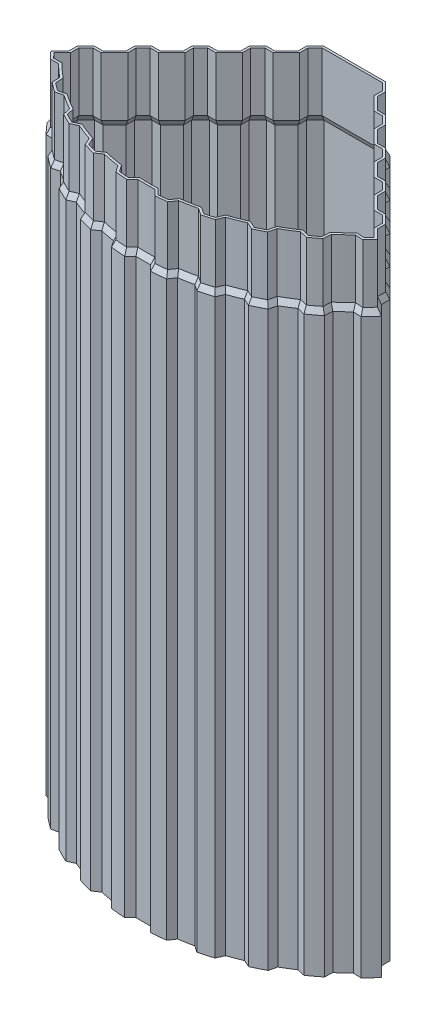
SolidWorks part; units mm, degrees
ref_plane "Front Plane" through (0, 0, 0) normal (0, 0, 1) x (1, 0, 0)
ref_plane "Top Plane" through (0, 0, 0) normal (0, 1, 0) x (1, 0, 0)
ref_plane "Right Plane" through (0, 0, 0) normal (1, 0, 0) x (0, 0, -1)
sketch "Sketch1" plane through (0, 0, 0) normal (0, 1, 0) x (1, 0, 0)
  line L3 (0, 0) -> (0, -48.7896) construction
  line L4 (0, -48.7896) -> (-56.9612, -48.7896) construction
  line L5 (0, -48.7896) -> (56.9612, -48.7896) construction
  line L11 (-11, 0) -> (11, 0)
  line L12 (-14.4647, -3.4647) -> (-11, 0)
  line L14 (-14.4647, -3.4647) -> (-14.4647, -6.2932)
  line L15 (-14.4647, -6.2932) -> (-17.9295, -9.7579)
  line L16 (-17.9295, -9.7579) -> (-20.7579, -9.7579)
  line L17 (-20.7579, -9.7579) -> (-24.2227, -13.2227)
  line L18 (-30.5158, -19.5158) -> (-33.9806, -22.9806)
  line L19 (-27.6874, -19.5158) -> (-30.5158, -19.5158)
  line L20 (-24.2227, -16.0511) -> (-27.6874, -19.5158)
  line L21 (-24.2227, -13.2227) -> (-24.2227, -16.0511)
  line L22 (-40.2738, -29.2738) -> (-43.7385, -32.7385)
  line L23 (-37.4453, -29.2738) -> (-40.2738, -29.2738)
  line L24 (-33.9806, -25.809) -> (-37.4453, -29.2738)
  line L25 (-33.9806, -22.9806) -> (-33.9806, -25.809)
  line L26 (-50.0317, -39.0317) -> (-53.4964, -42.4964)
  line L27 (-47.2033, -39.0317) -> (-50.0317, -39.0317)
  line L28 (-43.7385, -35.5669) -> (-47.2033, -39.0317)
  line L29 (-43.7385, -32.7385) -> (-43.7385, -35.5669)
  line L31 (53.4964, -42.4964) -> (53.4964, -45.3249)
  line L32 (-53.4964, -45.3249) -> (-56.9612, -48.7896)
  line L33 (-53.4964, -42.4964) -> (-53.4964, -45.3249)
  line L34 (-56.9612, -48.7896) -> (-59.7896, -48.7896) [skipped]
  line L35 (-59.7896, -48.7896) -> (-63.2543, -52.2543) [skipped]
  line L36 (53.4964, -45.3249) -> (56.9612, -48.7896)
  line L38 (43.7385, -32.7385) -> (43.7385, -35.5669)
  line L39 (43.7385, -35.5669) -> (47.2033, -39.0317)
  line L40 (47.2033, -39.0317) -> (50.0317, -39.0317)
  line L41 (50.0317, -39.0317) -> (53.4964, -42.4964)
  line L42 (33.9806, -22.9806) -> (33.9806, -25.809)
  line L43 (33.9806, -25.809) -> (37.4453, -29.2738)
  line L44 (37.4453, -29.2738) -> (40.2738, -29.2738)
  line L45 (40.2738, -29.2738) -> (43.7385, -32.7385)
  line L46 (24.2227, -13.2227) -> (24.2227, -16.0511)
  line L47 (24.2227, -16.0511) -> (27.6874, -19.5158)
  line L48 (27.6874, -19.5158) -> (30.5158, -19.5158)
  line L49 (30.5158, -19.5158) -> (33.9806, -22.9806)
  line L50 (20.7579, -9.7579) -> (24.2227, -13.2227)
  line L51 (17.9295, -9.7579) -> (20.7579, -9.7579)
  line L52 (14.4647, -6.2932) -> (17.9295, -9.7579)
  line L53 (14.4647, -3.4647) -> (14.4647, -6.2932)
  line L54 (11, 0) -> (14.4647, -3.4647)
  line L55 (-53.6221, -52.4373) -> (-50.9199, -52.3083)
  line L56 (-47.2198, -55.6713) -> (-47.0908, -58.3734)
  line L57 (-53.6221, -52.4373) -> (-56.9612, -48.7896) construction
  line L58 (-43.0968, -61.3813) -> (-40.4641, -60.759)
  line L59 (-36.2101, -63.3864) -> (-35.5877, -66.019)
  line L60 (-31.1098, -68.2435) -> (-28.6359, -67.149)
  line L61 (-23.9722, -68.9517) -> (-22.8776, -71.4256)
  line L62 (-18.0677, -72.7912) -> (-15.8365, -71.2615)
  line L63 (-10.9213, -72.1784) -> (-9.3916, -74.4097)
  line L64 (-4.4129, -74.8701) -> (-2.5, -72.9572)
  line L65 (2.5, -72.9572) -> (4.4129, -74.8701)
  line L66 (9.3916, -74.4097) -> (10.9213, -72.1784)
  line L67 (15.8365, -71.2615) -> (18.0677, -72.7912)
  line L68 (22.8776, -71.4256) -> (23.9722, -68.9517)
  line L69 (28.6359, -67.149) -> (31.1098, -68.2435)
  line L70 (35.5877, -66.019) -> (36.2101, -63.3864)
  line L71 (40.4641, -60.759) -> (43.0968, -61.3813)
  line L72 (47.0908, -58.3734) -> (47.2198, -55.6713)
  line L73 (50.9199, -52.3083) -> (53.6221, -52.4373)
  line L74 (53.6221, -52.4373) -> (56.9612, -48.7896) construction
  arc A0 (-56.9612, -48.7896) -> (-53.6221, -52.4373) centre (0, 0) ccw
  arc A2 (-36.2902, -47.7807) -> (36.2902, -47.7807) centre (0, 0) ccw construction
  circle A3 centre (0, -59.9997) radius 1.7
  circle A4 centre (-34.922, -48.7896) radius 1.7
  circle A5 centre (34.922, -48.7896) radius 1.7
  circle A6 centre (0, -26) radius 1.7
  arc A8 (-55.5426, -47.3711) -> (-54.3008, -48.7896) centre (0, 0) ccw construction
  arc A9 (-47.0908, -58.3734) -> (-43.0968, -61.3813) centre (0, 0) ccw
  arc A10 (-50.9199, -52.3083) -> (-47.2198, -55.6713) centre (0, 0) ccw
  arc A11 (-40.4641, -60.759) -> (-36.2101, -63.3864) centre (0, 0) ccw
  arc A12 (-35.5877, -66.019) -> (-31.1098, -68.2435) centre (0, 0) ccw
  arc A13 (-28.6359, -67.149) -> (-23.9722, -68.9517) centre (0, 0) ccw
  arc A14 (-22.8776, -71.4256) -> (-18.0677, -72.7912) centre (0, 0) ccw
  arc A15 (-15.8365, -71.2615) -> (-10.9213, -72.1784) centre (0, 0) ccw
  arc A16 (-9.3916, -74.4097) -> (-4.4129, -74.8701) centre (0, 0) ccw
  arc A17 (-2.5, -72.9572) -> (2.5, -72.9572) centre (0, 0) ccw
  arc A18 (4.4129, -74.8701) -> (9.3916, -74.4097) centre (0, 0) ccw
  arc A19 (10.9213, -72.1784) -> (15.8365, -71.2615) centre (0, 0) ccw
  arc A20 (18.0677, -72.7912) -> (22.8776, -71.4256) centre (0, 0) ccw
  arc A21 (23.9722, -68.9517) -> (28.6359, -67.149) centre (0, 0) ccw
  arc A22 (31.1098, -68.2435) -> (35.5877, -66.019) centre (0, 0) ccw
  arc A23 (36.2101, -63.3864) -> (40.4641, -60.759) centre (0, 0) ccw
  arc A24 (43.0968, -61.3813) -> (47.0908, -58.3734) centre (0, 0) ccw
  arc A25 (47.2198, -55.6713) -> (50.9199, -52.3083) centre (0, 0) ccw
  arc A26 (53.6221, -52.4373) -> (56.9612, -48.7896) centre (0, 0) ccw
  arc A27 (54.3008, -48.7896) -> (55.5426, -47.3711) centre (0, 0) ccw construction
  point P36 (0, 0)
  point P42 (0, 0)
  point P97 (0, 0)
  point P98 (0, 0)
  point P101 (0, 0)
  dimension "D2" = 75
  dimension "D4" = 3.4
  dimension "D5" = 15.0003
  dimension "D7" = 135
  dimension "D9" = 2
  dimension "D1" = 22
  dimension "D3" = 135
  dimension "D6" = 26
  dimension "D8" = 2
  dimension "D10" = 90
  dimension "D12" = 90
  dimension "D13" = 5
  dimension "D14" = 4.8999
  dimension "D15" = 9
  dimension "D16" = 5
  dimension "D11" = 5
extrude "Extrude-Thin2" add sketch "Sketch1" along normal blind 195 thin contours L11 L54 L53 L52 L51 L50 L46 L47 L48 L49 L42 L43 L44 L45 L38 L39 L40 L41 L31 L36 A26 L73 A25 L72 A24 L71 A23 L70 A22 L69 A21 L68 A20 L67 A19 L66 A18 L65 A17 L64 A16 L63 A15 L62 A14 L61 A13 L60 A12 L59 A11 L58 A9 L56 A10 L55 A0 L32 L33 L26 L27 L28 L29 L22 L23 L24 L25 L18 L19 L20 L21 L17 L16 L15 L14 L12 thin type one direction reverse wall 0.8
ref_plane "Plane1" through (0, 197, 0) normal (0, 1, 0) x (1, 0, 0)
sketch "Sketch7" plane through (0, 197, 0) normal (0, 1, 0) x (1, 0, 0)
  line L6 (13.4647, -3.879) -> (10.5858, -1)
  line L7 (10.5858, -1) -> (-10.5858, -1)
  line L8 (13.4647, -3.879) -> (10.5858, -1)
  line L10 (10.5858, -1) -> (-10.5858, -1)
  line L47 (-10.5858, -1) -> (-13.4647, -3.879)
  line L48 (-10.5858, -1) -> (-13.4647, -3.879)
  line L49 (-13.4647, -3.879) -> (-13.4647, -6.7074)
  line L50 (-13.4647, -3.879) -> (-13.4647, -6.7074)
  line L51 (-13.4647, -6.7074) -> (-17.5153, -10.7579)
  line L52 (-13.4647, -6.7074) -> (-17.5153, -10.7579)
  line L53 (-17.5153, -10.7579) -> (-20.3437, -10.7579)
  line L54 (-17.5153, -10.7579) -> (-20.3437, -10.7579)
  line L55 (-20.3437, -10.7579) -> (-23.2227, -13.6369)
  line L56 (-20.3437, -10.7579) -> (-23.2227, -13.6369)
  line L57 (-23.2227, -13.6369) -> (-23.2227, -16.4653)
  line L58 (-23.2227, -13.6369) -> (-23.2227, -16.4653)
  line L59 (-23.2227, -16.4653) -> (-27.2732, -20.5158)
  line L60 (-23.2227, -16.4653) -> (-27.2732, -20.5158)
  line L61 (-27.2732, -20.5158) -> (-30.1016, -20.5158)
  line L62 (-27.2732, -20.5158) -> (-30.1016, -20.5158)
  line L63 (-30.1016, -20.5158) -> (-32.9806, -23.3948)
  line L64 (-30.1016, -20.5158) -> (-32.9806, -23.3948)
  line L65 (-32.9806, -23.3948) -> (-32.9806, -26.2232)
  line L66 (-32.9806, -23.3948) -> (-32.9806, -26.2232)
  line L67 (-32.9806, -26.2232) -> (-37.0311, -30.2738)
  line L68 (-32.9806, -26.2232) -> (-37.0311, -30.2738)
  line L69 (-37.0311, -30.2738) -> (-39.8595, -30.2738)
  line L70 (-37.0311, -30.2738) -> (-39.8595, -30.2738)
  line L71 (-39.8595, -30.2738) -> (-42.7385, -33.1527)
  line L72 (-39.8595, -30.2738) -> (-42.7385, -33.1527)
  line L73 (-42.7385, -33.1527) -> (-42.7385, -35.9811)
  line L74 (-42.7385, -33.1527) -> (-42.7385, -35.9811)
  line L75 (-42.7385, -35.9811) -> (-46.789, -40.0317)
  line L76 (-42.7385, -35.9811) -> (-46.789, -40.0317)
  line L77 (-46.789, -40.0317) -> (-49.6175, -40.0317)
  line L78 (-46.789, -40.0317) -> (-49.6175, -40.0317)
  line L79 (-49.6175, -40.0317) -> (-52.4964, -42.9106)
  line L80 (-49.6175, -40.0317) -> (-52.4964, -42.9106)
  line L81 (-52.4964, -42.9106) -> (-52.4964, -45.7391)
  line L82 (-52.4964, -42.9106) -> (-52.4964, -45.7391)
  line L83 (-52.4964, -45.7391) -> (-55.5954, -48.838)
  line L84 (-52.4964, -45.7391) -> (-55.5954, -48.838)
  line L85 (-53.2193, -51.417) -> (-50.5319, -51.2887)
  line L87 (-53.2193, -51.417) -> (-50.5319, -51.2887)
  line L89 (55.5954, -48.838) -> (52.4964, -45.7391)
  line L90 (55.5954, -48.838) -> (52.4964, -45.7391)
  line L91 (52.4964, -45.7391) -> (52.4964, -42.9106)
  line L92 (52.4964, -45.7391) -> (52.4964, -42.9106)
  line L93 (52.4964, -42.9106) -> (49.6175, -40.0317)
  line L94 (52.4964, -42.9106) -> (49.6175, -40.0317)
  line L95 (49.6175, -40.0317) -> (46.789, -40.0317)
  line L96 (49.6175, -40.0317) -> (46.789, -40.0317)
  line L97 (46.789, -40.0317) -> (42.7385, -35.9811)
  line L98 (46.789, -40.0317) -> (42.7385, -35.9811)
  line L99 (42.7385, -35.9811) -> (42.7385, -33.1527)
  line L100 (42.7385, -35.9811) -> (42.7385, -33.1527)
  line L101 (42.7385, -33.1527) -> (39.8595, -30.2738)
  line L102 (42.7385, -33.1527) -> (39.8595, -30.2738)
  line L103 (39.8595, -30.2738) -> (37.0311, -30.2738)
  line L104 (39.8595, -30.2738) -> (37.0311, -30.2738)
  line L105 (37.0311, -30.2738) -> (32.9806, -26.2232)
  line L106 (37.0311, -30.2738) -> (32.9806, -26.2232)
  line L107 (32.9806, -26.2232) -> (32.9806, -23.3948)
  line L108 (32.9806, -26.2232) -> (32.9806, -23.3948)
  line L109 (32.9806, -23.3948) -> (30.1016, -20.5158)
  line L110 (32.9806, -23.3948) -> (30.1016, -20.5158)
  line L111 (30.1016, -20.5158) -> (27.2732, -20.5158)
  line L112 (30.1016, -20.5158) -> (27.2732, -20.5158)
  line L113 (27.2732, -20.5158) -> (23.2227, -16.4653)
  line L114 (27.2732, -20.5158) -> (23.2227, -16.4653)
  line L115 (23.2227, -16.4653) -> (23.2227, -13.6369)
  line L116 (23.2227, -16.4653) -> (23.2227, -13.6369)
  line L117 (23.2227, -13.6369) -> (20.3437, -10.7579)
  line L118 (23.2227, -13.6369) -> (20.3437, -10.7579)
  line L119 (20.3437, -10.7579) -> (17.5153, -10.7579)
  line L120 (20.3437, -10.7579) -> (17.5153, -10.7579)
  line L121 (17.5153, -10.7579) -> (13.4647, -6.7074)
  line L122 (17.5153, -10.7579) -> (13.4647, -6.7074)
  line L123 (13.4647, -6.7074) -> (13.4647, -3.879)
  line L124 (13.4647, -6.7074) -> (13.4647, -3.879)
  line L141 (-46.2418, -55.1879) -> (-46.1135, -57.8753)
  line L142 (-46.2418, -55.1879) -> (-46.1135, -57.8753)
  line L143 (-42.888, -60.3044) -> (-40.2696, -59.6855)
  line L144 (-42.888, -60.3044) -> (-40.2696, -59.6855)
  line L145 (-35.3372, -62.7318) -> (-34.7183, -65.3501)
  line L146 (-35.3372, -62.7318) -> (-34.7183, -65.3501)
  line L147 (-31.102, -67.1466) -> (-28.6416, -66.058)
  line L148 (-31.102, -67.1466) -> (-28.6416, -66.058)
  line L149 (-23.2342, -68.1482) -> (-22.1456, -70.6086)
  line L150 (-23.2342, -68.1482) -> (-22.1456, -70.6086)
  line L151 (-18.2613, -71.7114) -> (-16.0422, -70.1901)
  line L152 (-18.2613, -71.7114) -> (-16.0422, -70.1901)
  line L153 (-10.3432, -71.2532) -> (-8.8218, -73.4723)
  line L154 (-10.3432, -71.2532) -> (-8.8218, -73.4723)
  line L155 (-4.8011, -73.8441) -> (-2.8987, -71.9416)
  line L156 (-4.8011, -73.8441) -> (-2.8987, -71.9416)
  line L157 (2.8987, -71.9416) -> (4.8011, -73.8441)
  line L158 (2.8987, -71.9416) -> (4.8011, -73.8441)
  line L159 (8.8218, -73.4723) -> (10.3432, -71.2532)
  line L160 (8.8218, -73.4723) -> (10.3432, -71.2532)
  line L161 (16.0422, -70.1901) -> (18.2613, -71.7114)
  line L162 (16.0422, -70.1901) -> (18.2613, -71.7114)
  line L163 (22.1456, -70.6086) -> (23.2342, -68.1482)
  line L164 (22.1456, -70.6086) -> (23.2342, -68.1482)
  line L165 (28.6416, -66.058) -> (31.102, -67.1466)
  line L166 (28.6416, -66.058) -> (31.102, -67.1466)
  line L167 (34.7183, -65.3501) -> (35.3372, -62.7318)
  line L168 (34.7183, -65.3501) -> (35.3372, -62.7318)
  line L169 (40.2696, -59.6855) -> (42.888, -60.3044)
  line L170 (40.2696, -59.6855) -> (42.888, -60.3044)
  line L171 (46.1135, -57.8753) -> (46.2418, -55.1879)
  line L172 (46.1135, -57.8753) -> (46.2418, -55.1879)
  line L173 (50.5319, -51.2887) -> (53.2193, -51.417)
  line L174 (50.5319, -51.2887) -> (53.2193, -51.417)
  arc A2 (-55.5954, -48.838) -> (-53.2193, -51.417) centre (0, 0) ccw
  arc A3 (-55.5954, -48.838) -> (-53.2193, -51.417) centre (0, 0) ccw
  arc A21 (-50.5319, -51.2887) -> (-46.2418, -55.1879) centre (0, 0) ccw
  arc A22 (-50.5319, -51.2887) -> (-46.2418, -55.1879) centre (0, 0) ccw
  arc A23 (-46.1135, -57.8753) -> (-42.888, -60.3044) centre (0, 0) ccw
  arc A24 (-46.1135, -57.8753) -> (-42.888, -60.3044) centre (0, 0) ccw
  arc A25 (-40.2696, -59.6855) -> (-35.3372, -62.7318) centre (0, 0) ccw
  arc A26 (-40.2696, -59.6855) -> (-35.3372, -62.7318) centre (0, 0) ccw
  arc A27 (-34.7183, -65.3501) -> (-31.102, -67.1466) centre (0, 0) ccw
  arc A28 (-34.7183, -65.3501) -> (-31.102, -67.1466) centre (0, 0) ccw
  arc A29 (-28.6416, -66.058) -> (-23.2342, -68.1482) centre (0, 0) ccw
  arc A30 (-28.6416, -66.058) -> (-23.2342, -68.1482) centre (0, 0) ccw
  arc A31 (-22.1456, -70.6086) -> (-18.2613, -71.7114) centre (0, 0) ccw
  arc A32 (-22.1456, -70.6086) -> (-18.2613, -71.7114) centre (0, 0) ccw
  arc A33 (-16.0422, -70.1901) -> (-10.3432, -71.2532) centre (0, 0) ccw
  arc A34 (-16.0422, -70.1901) -> (-10.3432, -71.2532) centre (0, 0) ccw
  arc A35 (-8.8218, -73.4723) -> (-4.8011, -73.8441) centre (0, 0) ccw
  arc A36 (-8.8218, -73.4723) -> (-4.8011, -73.8441) centre (0, 0) ccw
  arc A37 (-2.8987, -71.9416) -> (2.8987, -71.9416) centre (0, 0) ccw
  arc A38 (-2.8987, -71.9416) -> (2.8987, -71.9416) centre (0, 0) ccw
  arc A39 (4.8011, -73.8441) -> (8.8218, -73.4723) centre (0, 0) ccw
  arc A40 (4.8011, -73.8441) -> (8.8218, -73.4723) centre (0, 0) ccw
  arc A41 (10.3432, -71.2532) -> (16.0422, -70.1901) centre (0, 0) ccw
  arc A42 (10.3432, -71.2532) -> (16.0422, -70.1901) centre (0, 0) ccw
  arc A43 (18.2613, -71.7114) -> (22.1456, -70.6086) centre (0, 0) ccw
  arc A44 (18.2613, -71.7114) -> (22.1456, -70.6086) centre (0, 0) ccw
  arc A45 (23.2342, -68.1482) -> (28.6416, -66.058) centre (0, 0) ccw
  arc A46 (23.2342, -68.1482) -> (28.6416, -66.058) centre (0, 0) ccw
  arc A47 (31.102, -67.1466) -> (34.7183, -65.3501) centre (0, 0) ccw
  arc A48 (31.102, -67.1466) -> (34.7183, -65.3501) centre (0, 0) ccw
  arc A49 (35.3372, -62.7318) -> (40.2696, -59.6855) centre (0, 0) ccw
  arc A50 (35.3372, -62.7318) -> (40.2696, -59.6855) centre (0, 0) ccw
  arc A51 (42.888, -60.3044) -> (46.1135, -57.8753) centre (0, 0) ccw
  arc A52 (42.888, -60.3044) -> (46.1135, -57.8753) centre (0, 0) ccw
  arc A53 (46.2418, -55.1879) -> (50.5319, -51.2887) centre (0, 0) ccw
  arc A54 (46.2418, -55.1879) -> (50.5319, -51.2887) centre (0, 0) ccw
  arc A55 (53.2193, -51.417) -> (55.5954, -48.838) centre (0, 0) ccw
  arc A56 (53.2193, -51.417) -> (55.5954, -48.838) centre (0, 0) ccw
  dimension "D1" = 1
extrude "Extrude-Thin3" add sketch "Sketch7" along normal blind 20 separate body thin thin type one direction reverse wall 0.8
sketch "Sketch8" plane through (0, 197, 0) normal (0, -1, 0) x (1, 0, 0)
  line L3 (13.4647, 3.879) -> (13.4647, 6.7074)
  line L4 (-10.5858, 1) -> (10.5858, 1)
  line L5 (13.4647, 3.879) -> (13.4647, 6.7074)
  line L7 (-10.5858, 1) -> (10.5858, 1)
  line L9 (-54.4967, 48.8707) -> (-51.6964, 46.0704)
  line L10 (-51.6964, 46.0704) -> (-51.6964, 43.242)
  line L11 (-51.6964, 43.242) -> (-49.2861, 40.8317)
  line L12 (-49.2861, 40.8317) -> (-46.4577, 40.8317)
  line L13 (-46.4577, 40.8317) -> (-41.9385, 36.3125)
  line L14 (-41.9385, 36.3125) -> (-41.9385, 33.4841)
  line L15 (-41.9385, 33.4841) -> (-39.5282, 31.0738)
  line L16 (-39.5282, 31.0738) -> (-36.6997, 31.0738)
  line L17 (-36.6997, 31.0738) -> (-32.1806, 26.5546)
  line L18 (-32.1806, 26.5546) -> (-32.1806, 23.7262)
  line L19 (-32.1806, 23.7262) -> (-29.7703, 21.3158)
  line L20 (-29.7703, 21.3158) -> (-26.9418, 21.3158)
  line L21 (-26.9418, 21.3158) -> (-22.4227, 16.7967)
  line L22 (-22.4227, 16.7967) -> (-22.4227, 13.9683)
  line L23 (-22.4227, 13.9683) -> (-20.0123, 11.5579)
  line L24 (-20.0123, 11.5579) -> (-17.1839, 11.5579)
  line L25 (-17.1839, 11.5579) -> (-12.6647, 7.0388)
  line L26 (-12.6647, 7.0388) -> (-12.6647, 4.2103)
  line L27 (-12.6647, 4.2103) -> (-10.2544, 1.8)
  line L28 (-10.2544, 1.8) -> (10.2544, 1.8)
  line L29 (10.2544, 1.8) -> (12.6647, 4.2103)
  line L30 (12.6647, 4.2103) -> (12.6647, 7.0388)
  line L31 (12.6647, 7.0388) -> (17.1839, 11.5579)
  line L32 (17.1839, 11.5579) -> (20.0123, 11.5579)
  line L33 (20.0123, 11.5579) -> (22.4227, 13.9683)
  line L34 (22.4227, 13.9683) -> (22.4227, 16.7967)
  line L35 (22.4227, 16.7967) -> (26.9418, 21.3158)
  line L36 (26.9418, 21.3158) -> (29.7703, 21.3158)
  line L37 (29.7703, 21.3158) -> (32.1806, 23.7262)
  line L38 (32.1806, 23.7262) -> (32.1806, 26.5546)
  line L39 (32.1806, 26.5546) -> (36.6997, 31.0738)
  line L40 (36.6997, 31.0738) -> (39.5282, 31.0738)
  line L41 (39.5282, 31.0738) -> (41.9385, 33.4841)
  line L42 (41.9385, 33.4841) -> (41.9385, 36.3125)
  line L43 (41.9385, 36.3125) -> (46.4577, 40.8317)
  line L44 (46.4577, 40.8317) -> (49.2861, 40.8317)
  line L45 (49.2861, 40.8317) -> (51.6964, 43.242)
  line L46 (51.6964, 43.242) -> (51.6964, 46.0704)
  line L47 (51.6964, 46.0704) -> (54.4967, 48.8707)
  line L48 (52.8945, 50.6005) -> (50.2189, 50.4728)
  line L49 (45.4594, 54.7985) -> (45.3317, 57.4741)
  line L50 (42.7183, 59.4423) -> (40.1115, 58.8261)
  line L51 (34.6396, 62.2056) -> (34.0233, 64.8124)
  line L52 (13.4647, 6.7074) -> (17.5153, 10.7579)
  line L53 (13.4647, 6.7074) -> (17.5153, 10.7579)
  line L54 (17.5153, 10.7579) -> (20.3437, 10.7579)
  line L55 (17.5153, 10.7579) -> (20.3437, 10.7579)
  line L56 (20.3437, 10.7579) -> (23.2227, 13.6369)
  line L57 (20.3437, 10.7579) -> (23.2227, 13.6369)
  line L58 (23.2227, 13.6369) -> (23.2227, 16.4653)
  line L59 (23.2227, 13.6369) -> (23.2227, 16.4653)
  line L60 (23.2227, 16.4653) -> (27.2732, 20.5158)
  line L61 (23.2227, 16.4653) -> (27.2732, 20.5158)
  line L62 (27.2732, 20.5158) -> (30.1016, 20.5158)
  line L63 (27.2732, 20.5158) -> (30.1016, 20.5158)
  line L64 (30.1016, 20.5158) -> (32.9806, 23.3948)
  line L65 (30.1016, 20.5158) -> (32.9806, 23.3948)
  line L66 (32.9806, 23.3948) -> (32.9806, 26.2232)
  line L67 (32.9806, 23.3948) -> (32.9806, 26.2232)
  line L68 (32.9806, 26.2232) -> (37.0311, 30.2738)
  line L69 (32.9806, 26.2232) -> (37.0311, 30.2738)
  line L70 (37.0311, 30.2738) -> (39.8595, 30.2738)
  line L71 (37.0311, 30.2738) -> (39.8595, 30.2738)
  line L72 (39.8595, 30.2738) -> (42.7385, 33.1527)
  line L73 (39.8595, 30.2738) -> (42.7385, 33.1527)
  line L74 (42.7385, 33.1527) -> (42.7385, 35.9811)
  line L75 (42.7385, 33.1527) -> (42.7385, 35.9811)
  line L76 (42.7385, 35.9811) -> (46.789, 40.0317)
  line L77 (42.7385, 35.9811) -> (46.789, 40.0317)
  line L78 (46.789, 40.0317) -> (49.6175, 40.0317)
  line L79 (46.789, 40.0317) -> (49.6175, 40.0317)
  line L80 (49.6175, 40.0317) -> (52.4964, 42.9106)
  line L81 (49.6175, 40.0317) -> (52.4964, 42.9106)
  line L82 (52.4964, 42.9106) -> (52.4964, 45.7391)
  line L83 (52.4964, 42.9106) -> (52.4964, 45.7391)
  line L84 (52.4964, 45.7391) -> (55.5954, 48.838)
  line L85 (52.4964, 45.7391) -> (55.5954, 48.838)
  line L86 (53.2193, 51.417) -> (50.5319, 51.2887)
  line L88 (53.2193, 51.417) -> (50.5319, 51.2887)
  line L90 (-55.5954, 48.838) -> (-52.4964, 45.7391)
  line L91 (-55.5954, 48.838) -> (-52.4964, 45.7391)
  line L92 (-52.4964, 45.7391) -> (-52.4964, 42.9106)
  line L93 (-52.4964, 45.7391) -> (-52.4964, 42.9106)
  line L94 (-52.4964, 42.9106) -> (-49.6175, 40.0317)
  line L95 (-52.4964, 42.9106) -> (-49.6175, 40.0317)
  line L96 (-49.6175, 40.0317) -> (-46.789, 40.0317)
  line L97 (-49.6175, 40.0317) -> (-46.789, 40.0317)
  line L98 (-46.789, 40.0317) -> (-42.7385, 35.9811)
  line L99 (-46.789, 40.0317) -> (-42.7385, 35.9811)
  line L100 (-42.7385, 35.9811) -> (-42.7385, 33.1527)
  line L101 (-42.7385, 35.9811) -> (-42.7385, 33.1527)
  line L102 (-42.7385, 33.1527) -> (-39.8595, 30.2738)
  line L103 (-42.7385, 33.1527) -> (-39.8595, 30.2738)
  line L104 (-39.8595, 30.2738) -> (-37.0311, 30.2738)
  line L105 (-39.8595, 30.2738) -> (-37.0311, 30.2738)
  line L106 (-37.0311, 30.2738) -> (-32.9806, 26.2232)
  line L107 (-37.0311, 30.2738) -> (-32.9806, 26.2232)
  line L108 (-32.9806, 26.2232) -> (-32.9806, 23.3948)
  line L109 (-32.9806, 26.2232) -> (-32.9806, 23.3948)
  line L110 (-32.9806, 23.3948) -> (-30.1016, 20.5158)
  line L111 (-32.9806, 23.3948) -> (-30.1016, 20.5158)
  line L112 (-30.1016, 20.5158) -> (-27.2732, 20.5158)
  line L113 (-30.1016, 20.5158) -> (-27.2732, 20.5158)
  line L114 (-27.2732, 20.5158) -> (-23.2227, 16.4653)
  line L115 (-27.2732, 20.5158) -> (-23.2227, 16.4653)
  line L116 (-23.2227, 16.4653) -> (-23.2227, 13.6369)
  line L117 (-23.2227, 16.4653) -> (-23.2227, 13.6369)
  line L118 (-23.2227, 13.6369) -> (-20.3437, 10.7579)
  line L119 (-23.2227, 13.6369) -> (-20.3437, 10.7579)
  line L120 (-20.3437, 10.7579) -> (-17.5153, 10.7579)
  line L121 (-20.3437, 10.7579) -> (-17.5153, 10.7579)
  line L122 (-17.5153, 10.7579) -> (-13.4647, 6.7074)
  line L123 (-17.5153, 10.7579) -> (-13.4647, 6.7074)
  line L124 (-13.4647, 6.7074) -> (-13.4647, 3.879)
  line L125 (-13.4647, 6.7074) -> (-13.4647, 3.879)
  line L126 (-13.4647, 3.879) -> (-10.5858, 1)
  line L127 (-13.4647, 3.879) -> (-10.5858, 1)
  line L128 (10.5858, 1) -> (13.4647, 3.879)
  line L129 (10.5858, 1) -> (13.4647, 3.879)
  line L130 (31.0934, 66.2679) -> (28.6438, 65.1841)
  line L131 (22.6449, 67.503) -> (21.5611, 69.9526)
  line L132 (18.4139, 70.8461) -> (16.2046, 69.3315)
  line L133 (9.8821, 70.5109) -> (8.3675, 72.7202)
  line L134 (5.1098, 73.0214) -> (3.2157, 71.1273)
  line L135 (-3.2157, 71.1273) -> (-5.1098, 73.0214)
  line L136 (-8.3675, 72.7202) -> (-9.8821, 70.5109)
  line L137 (-16.2046, 69.3315) -> (-18.4139, 70.8461)
  line L138 (-21.5611, 69.9526) -> (-22.6449, 67.503)
  line L139 (-28.6438, 65.1841) -> (-31.0934, 66.2679)
  line L140 (-34.0233, 64.8124) -> (-34.6396, 62.2056)
  line L141 (-40.1115, 58.8261) -> (-42.7183, 59.4423)
  line L142 (-45.3317, 57.4741) -> (-45.4594, 54.7985)
  line L143 (-50.2189, 50.4728) -> (-52.8945, 50.6005)
  line L146 (46.2418, 55.1879) -> (46.1135, 57.8753)
  line L147 (46.2418, 55.1879) -> (46.1135, 57.8753)
  line L148 (42.888, 60.3044) -> (40.2696, 59.6855)
  line L149 (42.888, 60.3044) -> (40.2696, 59.6855)
  line L150 (35.3372, 62.7318) -> (34.7183, 65.3501)
  line L151 (35.3372, 62.7318) -> (34.7183, 65.3501)
  line L152 (31.102, 67.1466) -> (28.6416, 66.058)
  line L153 (31.102, 67.1466) -> (28.6416, 66.058)
  line L154 (23.2342, 68.1482) -> (22.1456, 70.6086)
  line L155 (23.2342, 68.1482) -> (22.1456, 70.6086)
  line L156 (18.2613, 71.7114) -> (16.0422, 70.1901)
  line L157 (18.2613, 71.7114) -> (16.0422, 70.1901)
  line L158 (10.3432, 71.2532) -> (8.8218, 73.4723)
  line L159 (10.3432, 71.2532) -> (8.8218, 73.4723)
  line L160 (4.8011, 73.8441) -> (2.8987, 71.9416)
  line L161 (4.8011, 73.8441) -> (2.8987, 71.9416)
  line L162 (-2.8987, 71.9416) -> (-4.8011, 73.8441)
  line L163 (-2.8987, 71.9416) -> (-4.8011, 73.8441)
  line L164 (-8.8218, 73.4723) -> (-10.3432, 71.2532)
  line L165 (-8.8218, 73.4723) -> (-10.3432, 71.2532)
  line L166 (-16.0422, 70.1901) -> (-18.2613, 71.7114)
  line L167 (-16.0422, 70.1901) -> (-18.2613, 71.7114)
  line L168 (-22.1456, 70.6086) -> (-23.2342, 68.1482)
  line L169 (-22.1456, 70.6086) -> (-23.2342, 68.1482)
  line L170 (-28.6416, 66.058) -> (-31.102, 67.1466)
  line L171 (-28.6416, 66.058) -> (-31.102, 67.1466)
  line L172 (-34.7183, 65.3501) -> (-35.3372, 62.7318)
  line L173 (-34.7183, 65.3501) -> (-35.3372, 62.7318)
  line L174 (-40.2696, 59.6855) -> (-42.888, 60.3044)
  line L175 (-40.2696, 59.6855) -> (-42.888, 60.3044)
  line L176 (-46.1135, 57.8753) -> (-46.2418, 55.1879)
  line L177 (-46.1135, 57.8753) -> (-46.2418, 55.1879)
  line L178 (-50.5319, 51.2887) -> (-53.2193, 51.417)
  line L179 (-50.5319, 51.2887) -> (-53.2193, 51.417)
  arc A1 (-53.2193, 51.417) -> (-55.5954, 48.838) centre (0, 0) ccw
  arc A2 (-53.2193, 51.417) -> (-55.5954, 48.838) centre (0, 0) ccw
  arc A3 (54.4967, 48.8707) -> (52.8945, 50.6005) centre (0, 0) ccw
  arc A4 (50.2189, 50.4728) -> (45.4594, 54.7985) centre (0, 0) ccw
  arc A5 (45.3317, 57.4741) -> (42.7183, 59.4423) centre (0, 0) ccw
  arc A6 (40.1115, 58.8261) -> (34.6396, 62.2056) centre (0, 0) ccw
  arc A7 (34.0233, 64.8124) -> (31.0934, 66.2679) centre (0, 0) ccw
  arc A8 (28.6438, 65.1841) -> (22.6449, 67.503) centre (0, 0) ccw
  arc A9 (21.5611, 69.9526) -> (18.4139, 70.8461) centre (0, 0) ccw
  arc A10 (16.2046, 69.3315) -> (9.8821, 70.5109) centre (0, 0) ccw
  arc A11 (8.3675, 72.7202) -> (5.1098, 73.0214) centre (0, 0) ccw
  arc A12 (3.2157, 71.1273) -> (-3.2157, 71.1273) centre (0, 0) ccw
  arc A13 (-5.1098, 73.0214) -> (-8.3675, 72.7202) centre (0, 0) ccw
  arc A14 (-9.8821, 70.5109) -> (-16.2046, 69.3315) centre (0, 0) ccw
  arc A15 (-18.4139, 70.8461) -> (-21.5611, 69.9526) centre (0, 0) ccw
  arc A16 (-22.6449, 67.503) -> (-28.6438, 65.1841) centre (0, 0) ccw
  arc A17 (-31.0934, 66.2679) -> (-34.0233, 64.8124) centre (0, 0) ccw
  arc A18 (-34.6396, 62.2056) -> (-40.1115, 58.8261) centre (0, 0) ccw
  arc A19 (-42.7183, 59.4423) -> (-45.3317, 57.4741) centre (0, 0) ccw
  arc A20 (-45.4594, 54.7985) -> (-50.2189, 50.4728) centre (0, 0) ccw
  arc A21 (-52.8945, 50.6005) -> (-54.4967, 48.8707) centre (0, 0) ccw
  arc A22 (55.5954, 48.838) -> (53.2193, 51.417) centre (0, 0) ccw
  arc A23 (55.5954, 48.838) -> (53.2193, 51.417) centre (0, 0) ccw
  arc A24 (50.5319, 51.2887) -> (46.2418, 55.1879) centre (0, 0) ccw
  arc A25 (50.5319, 51.2887) -> (46.2418, 55.1879) centre (0, 0) ccw
  arc A26 (46.1135, 57.8753) -> (42.888, 60.3044) centre (0, 0) ccw
  arc A27 (46.1135, 57.8753) -> (42.888, 60.3044) centre (0, 0) ccw
  arc A28 (40.2696, 59.6855) -> (35.3372, 62.7318) centre (0, 0) ccw
  arc A29 (40.2696, 59.6855) -> (35.3372, 62.7318) centre (0, 0) ccw
  arc A30 (34.7183, 65.3501) -> (31.102, 67.1466) centre (0, 0) ccw
  arc A31 (34.7183, 65.3501) -> (31.102, 67.1466) centre (0, 0) ccw
  arc A32 (28.6416, 66.058) -> (23.2342, 68.1482) centre (0, 0) ccw
  arc A33 (28.6416, 66.058) -> (23.2342, 68.1482) centre (0, 0) ccw
  arc A34 (22.1456, 70.6086) -> (18.2613, 71.7114) centre (0, 0) ccw
  arc A35 (22.1456, 70.6086) -> (18.2613, 71.7114) centre (0, 0) ccw
  arc A36 (16.0422, 70.1901) -> (10.3432, 71.2532) centre (0, 0) ccw
  arc A37 (16.0422, 70.1901) -> (10.3432, 71.2532) centre (0, 0) ccw
  arc A38 (8.8218, 73.4723) -> (4.8011, 73.8441) centre (0, 0) ccw
  arc A39 (8.8218, 73.4723) -> (4.8011, 73.8441) centre (0, 0) ccw
  arc A40 (2.8987, 71.9416) -> (-2.8987, 71.9416) centre (0, 0) ccw
  arc A41 (2.8987, 71.9416) -> (-2.8987, 71.9416) centre (0, 0) ccw
  arc A42 (-4.8011, 73.8441) -> (-8.8218, 73.4723) centre (0, 0) ccw
  arc A43 (-4.8011, 73.8441) -> (-8.8218, 73.4723) centre (0, 0) ccw
  arc A44 (-10.3432, 71.2532) -> (-16.0422, 70.1901) centre (0, 0) ccw
  arc A45 (-10.3432, 71.2532) -> (-16.0422, 70.1901) centre (0, 0) ccw
  arc A46 (-18.2613, 71.7114) -> (-22.1456, 70.6086) centre (0, 0) ccw
  arc A47 (-18.2613, 71.7114) -> (-22.1456, 70.6086) centre (0, 0) ccw
  arc A48 (-23.2342, 68.1482) -> (-28.6416, 66.058) centre (0, 0) ccw
  arc A49 (-23.2342, 68.1482) -> (-28.6416, 66.058) centre (0, 0) ccw
  arc A50 (-31.102, 67.1466) -> (-34.7183, 65.3501) centre (0, 0) ccw
  arc A51 (-31.102, 67.1466) -> (-34.7183, 65.3501) centre (0, 0) ccw
  arc A52 (-35.3372, 62.7318) -> (-40.2696, 59.6855) centre (0, 0) ccw
  arc A53 (-35.3372, 62.7318) -> (-40.2696, 59.6855) centre (0, 0) ccw
  arc A54 (-42.888, 60.3044) -> (-46.1135, 57.8753) centre (0, 0) ccw
  arc A55 (-42.888, 60.3044) -> (-46.1135, 57.8753) centre (0, 0) ccw
  arc A56 (-46.2418, 55.1879) -> (-50.5319, 51.2887) centre (0, 0) ccw
  arc A57 (-46.2418, 55.1879) -> (-50.5319, 51.2887) centre (0, 0) ccw
  dimension "D1" = 0
  dimension "D2" = 0.8
sketch "Sketch9" plane through (0, 195, 0) normal (0, 1, 0) x (1, 0, 0)
  line L3 (14.4647, -3.4647) -> (11, 0)
  line L4 (11, 0) -> (-11, 0)
  line L5 (14.4647, -3.4647) -> (11, 0)
  line L7 (11, 0) -> (-11, 0)
  line L9 (-53.3002, -51.6211) -> (-50.6098, -51.4926)
  line L10 (-46.4374, -55.2848) -> (-46.3089, -57.9752)
  line L11 (-42.93, -60.5199) -> (-40.3088, -59.9002)
  line L12 (-35.5117, -62.863) -> (-34.8921, -65.4842)
  line L13 (-31.1039, -67.3661) -> (-28.6407, -66.2763)
  line L14 (-23.3817, -68.3091) -> (-22.2919, -70.7722)
  line L15 (-18.2228, -71.9275) -> (-16.0013, -70.4045)
  line L16 (-10.4586, -71.4385) -> (-8.9356, -73.66)
  line L17 (-4.7237, -74.0495) -> (-2.8191, -72.1449)
  line L18 (2.8191, -72.1449) -> (4.7237, -74.0495)
  line L19 (8.9356, -73.66) -> (10.4586, -71.4385)
  line L20 (16.0013, -70.4045) -> (18.2228, -71.9275)
  line L21 (22.2919, -70.7722) -> (23.3817, -68.3091)
  line L22 (28.6407, -66.2763) -> (31.1039, -67.3661)
  line L23 (34.8921, -65.4842) -> (35.5117, -62.863)
  line L24 (40.3088, -59.9002) -> (42.93, -60.5199)
  line L25 (46.3089, -57.9752) -> (46.4374, -55.2848)
  line L26 (50.6098, -51.4926) -> (53.3002, -51.6211)
  line L27 (55.8692, -48.829) -> (52.6964, -45.6562)
  line L28 (52.6964, -45.6562) -> (52.6964, -42.8278)
  line L29 (52.6964, -42.8278) -> (49.7003, -39.8317)
  line L30 (49.7003, -39.8317) -> (46.8719, -39.8317)
  line L31 (46.8719, -39.8317) -> (42.9385, -35.8983)
  line L32 (42.9385, -35.8983) -> (42.9385, -33.0699)
  line L33 (42.9385, -33.0699) -> (39.9424, -30.0738)
  line L34 (39.9424, -30.0738) -> (37.114, -30.0738)
  line L35 (37.114, -30.0738) -> (33.1806, -26.1404)
  line L36 (33.1806, -26.1404) -> (33.1806, -23.312)
  line L37 (33.1806, -23.312) -> (30.1845, -20.3158)
  line L38 (30.1845, -20.3158) -> (27.356, -20.3158)
  line L39 (27.356, -20.3158) -> (23.4227, -16.3825)
  line L40 (23.4227, -16.3825) -> (23.4227, -13.554)
  line L41 (23.4227, -13.554) -> (20.4265, -10.5579)
  line L42 (20.4265, -10.5579) -> (17.5981, -10.5579)
  line L43 (17.5981, -10.5579) -> (13.6647, -6.6245)
  line L44 (13.6647, -6.6245) -> (13.6647, -3.7961)
  line L45 (13.6647, -3.7961) -> (10.6686, -0.8)
  line L46 (10.6686, -0.8) -> (-10.6686, -0.8)
  line L47 (-10.6686, -0.8) -> (-13.6647, -3.7961)
  line L48 (-13.6647, -3.7961) -> (-13.6647, -6.6245)
  line L49 (-13.6647, -6.6245) -> (-17.5981, -10.5579)
  line L50 (-17.5981, -10.5579) -> (-20.4265, -10.5579)
  line L51 (-20.4265, -10.5579) -> (-23.4227, -13.554)
  line L52 (-11, 0) -> (-14.4647, -3.4647)
  line L53 (-11, 0) -> (-14.4647, -3.4647)
  line L54 (-14.4647, -3.4647) -> (-14.4647, -6.2932)
  line L55 (-14.4647, -3.4647) -> (-14.4647, -6.2932)
  line L56 (-14.4647, -6.2932) -> (-17.9295, -9.7579)
  line L57 (-14.4647, -6.2932) -> (-17.9295, -9.7579)
  line L58 (-17.9295, -9.7579) -> (-20.7579, -9.7579)
  line L59 (-17.9295, -9.7579) -> (-20.7579, -9.7579)
  line L60 (-20.7579, -9.7579) -> (-24.2227, -13.2227)
  line L61 (-20.7579, -9.7579) -> (-24.2227, -13.2227)
  line L62 (-24.2227, -13.2227) -> (-24.2227, -16.0511)
  line L63 (-24.2227, -13.2227) -> (-24.2227, -16.0511)
  line L64 (-24.2227, -16.0511) -> (-27.6874, -19.5158)
  line L65 (-24.2227, -16.0511) -> (-27.6874, -19.5158)
  line L66 (-27.6874, -19.5158) -> (-30.5158, -19.5158)
  line L67 (-27.6874, -19.5158) -> (-30.5158, -19.5158)
  line L68 (-30.5158, -19.5158) -> (-33.9806, -22.9806)
  line L69 (-30.5158, -19.5158) -> (-33.9806, -22.9806)
  line L70 (-33.9806, -22.9806) -> (-33.9806, -25.809)
  line L71 (-33.9806, -22.9806) -> (-33.9806, -25.809)
  line L72 (-33.9806, -25.809) -> (-37.4453, -29.2738)
  line L73 (-33.9806, -25.809) -> (-37.4453, -29.2738)
  line L74 (-37.4453, -29.2738) -> (-40.2738, -29.2738)
  line L75 (-37.4453, -29.2738) -> (-40.2738, -29.2738)
  line L76 (-40.2738, -29.2738) -> (-43.7385, -32.7385)
  line L77 (-40.2738, -29.2738) -> (-43.7385, -32.7385)
  line L78 (-43.7385, -32.7385) -> (-43.7385, -35.5669)
  line L79 (-43.7385, -32.7385) -> (-43.7385, -35.5669)
  line L80 (-43.7385, -35.5669) -> (-47.2033, -39.0317)
  line L81 (-43.7385, -35.5669) -> (-47.2033, -39.0317)
  line L82 (-47.2033, -39.0317) -> (-50.0317, -39.0317)
  line L83 (-47.2033, -39.0317) -> (-50.0317, -39.0317)
  line L84 (-50.0317, -39.0317) -> (-53.4964, -42.4964)
  line L85 (-50.0317, -39.0317) -> (-53.4964, -42.4964)
  line L86 (-53.4964, -42.4964) -> (-53.4964, -45.3249)
  line L87 (-53.4964, -42.4964) -> (-53.4964, -45.3249)
  line L88 (-53.4964, -45.3249) -> (-56.9612, -48.7896)
  line L89 (-53.4964, -45.3249) -> (-56.9612, -48.7896)
  line L90 (-53.6221, -52.4373) -> (-50.9199, -52.3083)
  line L92 (-53.6221, -52.4373) -> (-50.9199, -52.3083)
  line L94 (56.9612, -48.7896) -> (53.4964, -45.3249)
  line L95 (56.9612, -48.7896) -> (53.4964, -45.3249)
  line L96 (53.4964, -45.3249) -> (53.4964, -42.4964)
  line L97 (53.4964, -45.3249) -> (53.4964, -42.4964)
  line L98 (53.4964, -42.4964) -> (50.0317, -39.0317)
  line L99 (53.4964, -42.4964) -> (50.0317, -39.0317)
  line L100 (50.0317, -39.0317) -> (47.2033, -39.0317)
  line L101 (50.0317, -39.0317) -> (47.2033, -39.0317)
  line L102 (47.2033, -39.0317) -> (43.7385, -35.5669)
  line L103 (47.2033, -39.0317) -> (43.7385, -35.5669)
  line L104 (43.7385, -35.5669) -> (43.7385, -32.7385)
  line L105 (43.7385, -35.5669) -> (43.7385, -32.7385)
  line L106 (43.7385, -32.7385) -> (40.2738, -29.2738)
  line L107 (43.7385, -32.7385) -> (40.2738, -29.2738)
  line L108 (40.2738, -29.2738) -> (37.4453, -29.2738)
  line L109 (40.2738, -29.2738) -> (37.4453, -29.2738)
  line L110 (37.4453, -29.2738) -> (33.9806, -25.809)
  line L111 (37.4453, -29.2738) -> (33.9806, -25.809)
  line L112 (33.9806, -25.809) -> (33.9806, -22.9806)
  line L113 (33.9806, -25.809) -> (33.9806, -22.9806)
  line L114 (33.9806, -22.9806) -> (30.5158, -19.5158)
  line L115 (33.9806, -22.9806) -> (30.5158, -19.5158)
  line L116 (30.5158, -19.5158) -> (27.6874, -19.5158)
  line L117 (30.5158, -19.5158) -> (27.6874, -19.5158)
  line L118 (27.6874, -19.5158) -> (24.2227, -16.0511)
  line L119 (27.6874, -19.5158) -> (24.2227, -16.0511)
  line L120 (24.2227, -16.0511) -> (24.2227, -13.2227)
  line L121 (24.2227, -16.0511) -> (24.2227, -13.2227)
  line L122 (24.2227, -13.2227) -> (20.7579, -9.7579)
  line L123 (24.2227, -13.2227) -> (20.7579, -9.7579)
  line L124 (20.7579, -9.7579) -> (17.9295, -9.7579)
  line L125 (20.7579, -9.7579) -> (17.9295, -9.7579)
  line L126 (17.9295, -9.7579) -> (14.4647, -6.2932)
  line L127 (17.9295, -9.7579) -> (14.4647, -6.2932)
  line L128 (14.4647, -6.2932) -> (14.4647, -3.4647)
  line L129 (14.4647, -6.2932) -> (14.4647, -3.4647)
  line L130 (-23.4227, -13.554) -> (-23.4227, -16.3825)
  line L131 (-23.4227, -16.3825) -> (-27.356, -20.3158)
  line L132 (-27.356, -20.3158) -> (-30.1845, -20.3158)
  line L133 (-30.1845, -20.3158) -> (-33.1806, -23.312)
  line L134 (-33.1806, -23.312) -> (-33.1806, -26.1404)
  line L135 (-33.1806, -26.1404) -> (-37.114, -30.0738)
  line L136 (-37.114, -30.0738) -> (-39.9424, -30.0738)
  line L137 (-39.9424, -30.0738) -> (-42.9385, -33.0699)
  line L138 (-42.9385, -33.0699) -> (-42.9385, -35.8983)
  line L139 (-42.9385, -35.8983) -> (-46.8719, -39.8317)
  line L140 (-46.8719, -39.8317) -> (-49.7003, -39.8317)
  line L141 (-49.7003, -39.8317) -> (-52.6964, -42.8278)
  line L142 (-52.6964, -42.8278) -> (-52.6964, -45.6562)
  line L143 (-52.6964, -45.6562) -> (-55.8692, -48.829)
  line L146 (-47.2198, -55.6713) -> (-47.0908, -58.3734)
  line L147 (-47.2198, -55.6713) -> (-47.0908, -58.3734)
  line L148 (-43.0968, -61.3813) -> (-40.4641, -60.759)
  line L149 (-43.0968, -61.3813) -> (-40.4641, -60.759)
  line L150 (-36.2101, -63.3864) -> (-35.5877, -66.019)
  line L151 (-36.2101, -63.3864) -> (-35.5877, -66.019)
  line L152 (-31.1098, -68.2435) -> (-28.6359, -67.149)
  line L153 (-31.1098, -68.2435) -> (-28.6359, -67.149)
  line L154 (-23.9722, -68.9517) -> (-22.8776, -71.4256)
  line L155 (-23.9722, -68.9517) -> (-22.8776, -71.4256)
  line L156 (-18.0677, -72.7912) -> (-15.8365, -71.2615)
  line L157 (-18.0677, -72.7912) -> (-15.8365, -71.2615)
  line L158 (-10.9213, -72.1784) -> (-9.3916, -74.4097)
  line L159 (-10.9213, -72.1784) -> (-9.3916, -74.4097)
  line L160 (-4.4129, -74.8701) -> (-2.5, -72.9572)
  line L161 (-4.4129, -74.8701) -> (-2.5, -72.9572)
  line L162 (2.5, -72.9572) -> (4.4129, -74.8701)
  line L163 (2.5, -72.9572) -> (4.4129, -74.8701)
  line L164 (9.3916, -74.4097) -> (10.9213, -72.1784)
  line L165 (9.3916, -74.4097) -> (10.9213, -72.1784)
  line L166 (15.8365, -71.2615) -> (18.0677, -72.7912)
  line L167 (15.8365, -71.2615) -> (18.0677, -72.7912)
  line L168 (22.8776, -71.4256) -> (23.9722, -68.9517)
  line L169 (22.8776, -71.4256) -> (23.9722, -68.9517)
  line L170 (28.6359, -67.149) -> (31.1098, -68.2435)
  line L171 (28.6359, -67.149) -> (31.1098, -68.2435)
  line L172 (35.5877, -66.019) -> (36.2101, -63.3864)
  line L173 (35.5877, -66.019) -> (36.2101, -63.3864)
  line L174 (40.4641, -60.759) -> (43.0968, -61.3813)
  line L175 (40.4641, -60.759) -> (43.0968, -61.3813)
  line L176 (47.0908, -58.3734) -> (47.2198, -55.6713)
  line L177 (47.0908, -58.3734) -> (47.2198, -55.6713)
  line L178 (50.9199, -52.3083) -> (53.6221, -52.4373)
  line L179 (50.9199, -52.3083) -> (53.6221, -52.4373)
  arc A1 (-56.9612, -48.7896) -> (-53.6221, -52.4373) centre (0, 0) ccw
  arc A2 (-56.9612, -48.7896) -> (-53.6221, -52.4373) centre (0, 0) ccw
  arc A3 (-55.8692, -48.829) -> (-53.3002, -51.6211) centre (0, 0) ccw
  arc A4 (-50.6098, -51.4926) -> (-46.4374, -55.2848) centre (0, 0) ccw
  arc A5 (-46.3089, -57.9752) -> (-42.93, -60.5199) centre (0, 0) ccw
  arc A6 (-40.3088, -59.9002) -> (-35.5117, -62.863) centre (0, 0) ccw
  arc A7 (-34.8921, -65.4842) -> (-31.1039, -67.3661) centre (0, 0) ccw
  arc A8 (-28.6407, -66.2763) -> (-23.3817, -68.3091) centre (0, 0) ccw
  arc A9 (-22.2919, -70.7722) -> (-18.2228, -71.9275) centre (0, 0) ccw
  arc A10 (-16.0013, -70.4045) -> (-10.4586, -71.4385) centre (0, 0) ccw
  arc A11 (-8.9356, -73.66) -> (-4.7237, -74.0495) centre (0, 0) ccw
  arc A12 (-2.8191, -72.1449) -> (2.8191, -72.1449) centre (0, 0) ccw
  arc A13 (4.7237, -74.0495) -> (8.9356, -73.66) centre (0, 0) ccw
  arc A14 (10.4586, -71.4385) -> (16.0013, -70.4045) centre (0, 0) ccw
  arc A15 (18.2228, -71.9275) -> (22.2919, -70.7722) centre (0, 0) ccw
  arc A16 (23.3817, -68.3091) -> (28.6407, -66.2763) centre (0, 0) ccw
  arc A17 (31.1039, -67.3661) -> (34.8921, -65.4842) centre (0, 0) ccw
  arc A18 (35.5117, -62.863) -> (40.3088, -59.9002) centre (0, 0) ccw
  arc A19 (42.93, -60.5199) -> (46.3089, -57.9752) centre (0, 0) ccw
  arc A20 (46.4374, -55.2848) -> (50.6098, -51.4926) centre (0, 0) ccw
  arc A21 (53.3002, -51.6211) -> (55.8692, -48.829) centre (0, 0) ccw
  arc A22 (-50.9199, -52.3083) -> (-47.2198, -55.6713) centre (0, 0) ccw
  arc A23 (-50.9199, -52.3083) -> (-47.2198, -55.6713) centre (0, 0) ccw
  arc A24 (-47.0908, -58.3734) -> (-43.0968, -61.3813) centre (0, 0) ccw
  arc A25 (-47.0908, -58.3734) -> (-43.0968, -61.3813) centre (0, 0) ccw
  arc A26 (-40.4641, -60.759) -> (-36.2101, -63.3864) centre (0, 0) ccw
  arc A27 (-40.4641, -60.759) -> (-36.2101, -63.3864) centre (0, 0) ccw
  arc A28 (-35.5877, -66.019) -> (-31.1098, -68.2435) centre (0, 0) ccw
  arc A29 (-35.5877, -66.019) -> (-31.1098, -68.2435) centre (0, 0) ccw
  arc A30 (-28.6359, -67.149) -> (-23.9722, -68.9517) centre (0, 0) ccw
  arc A31 (-28.6359, -67.149) -> (-23.9722, -68.9517) centre (0, 0) ccw
  arc A32 (-22.8776, -71.4256) -> (-18.0677, -72.7912) centre (0, 0) ccw
  arc A33 (-22.8776, -71.4256) -> (-18.0677, -72.7912) centre (0, 0) ccw
  arc A34 (-15.8365, -71.2615) -> (-10.9213, -72.1784) centre (0, 0) ccw
  arc A35 (-15.8365, -71.2615) -> (-10.9213, -72.1784) centre (0, 0) ccw
  arc A36 (-9.3916, -74.4097) -> (-4.4129, -74.8701) centre (0, 0) ccw
  arc A37 (-9.3916, -74.4097) -> (-4.4129, -74.8701) centre (0, 0) ccw
  arc A38 (-2.5, -72.9572) -> (2.5, -72.9572) centre (0, 0) ccw
  arc A39 (-2.5, -72.9572) -> (2.5, -72.9572) centre (0, 0) ccw
  arc A40 (4.4129, -74.8701) -> (9.3916, -74.4097) centre (0, 0) ccw
  arc A41 (4.4129, -74.8701) -> (9.3916, -74.4097) centre (0, 0) ccw
  arc A42 (10.9213, -72.1784) -> (15.8365, -71.2615) centre (0, 0) ccw
  arc A43 (10.9213, -72.1784) -> (15.8365, -71.2615) centre (0, 0) ccw
  arc A44 (18.0677, -72.7912) -> (22.8776, -71.4256) centre (0, 0) ccw
  arc A45 (18.0677, -72.7912) -> (22.8776, -71.4256) centre (0, 0) ccw
  arc A46 (23.9722, -68.9517) -> (28.6359, -67.149) centre (0, 0) ccw
  arc A47 (23.9722, -68.9517) -> (28.6359, -67.149) centre (0, 0) ccw
  arc A48 (31.1098, -68.2435) -> (35.5877, -66.019) centre (0, 0) ccw
  arc A49 (31.1098, -68.2435) -> (35.5877, -66.019) centre (0, 0) ccw
  arc A50 (36.2101, -63.3864) -> (40.4641, -60.759) centre (0, 0) ccw
  arc A51 (36.2101, -63.3864) -> (40.4641, -60.759) centre (0, 0) ccw
  arc A52 (43.0968, -61.3813) -> (47.0908, -58.3734) centre (0, 0) ccw
  arc A53 (43.0968, -61.3813) -> (47.0908, -58.3734) centre (0, 0) ccw
  arc A54 (47.2198, -55.6713) -> (50.9199, -52.3083) centre (0, 0) ccw
  arc A55 (47.2198, -55.6713) -> (50.9199, -52.3083) centre (0, 0) ccw
  arc A56 (53.6221, -52.4373) -> (56.9612, -48.7896) centre (0, 0) ccw
  arc A57 (53.6221, -52.4373) -> (56.9612, -48.7896) centre (0, 0) ccw
  dimension "D1" = 0
  dimension "D2" = 0.8
loft "Loft1" add section "Sketch9" section "Sketch8" connector at (-30.5158, 195, 19.5158) connector at (-30.1016, 197, 20.5158)
loft "Cut-Loft2" cut section "Sketch9<3>" section "Sketch8<3>" connector at (-20.4265, 195, 10.5579) connector at (-20.0123, 197, 11.5579)
sketch "Sketch9<3>" plane through (0, 195, 0) normal (0, 1, 0) x (1, 0, 0) same geometry as "Sketch9"
sketch "Sketch8<3>" plane through (0, 197, 0) normal (0, -1, 0) x (1, 0, 0) same geometry as "Sketch8"
